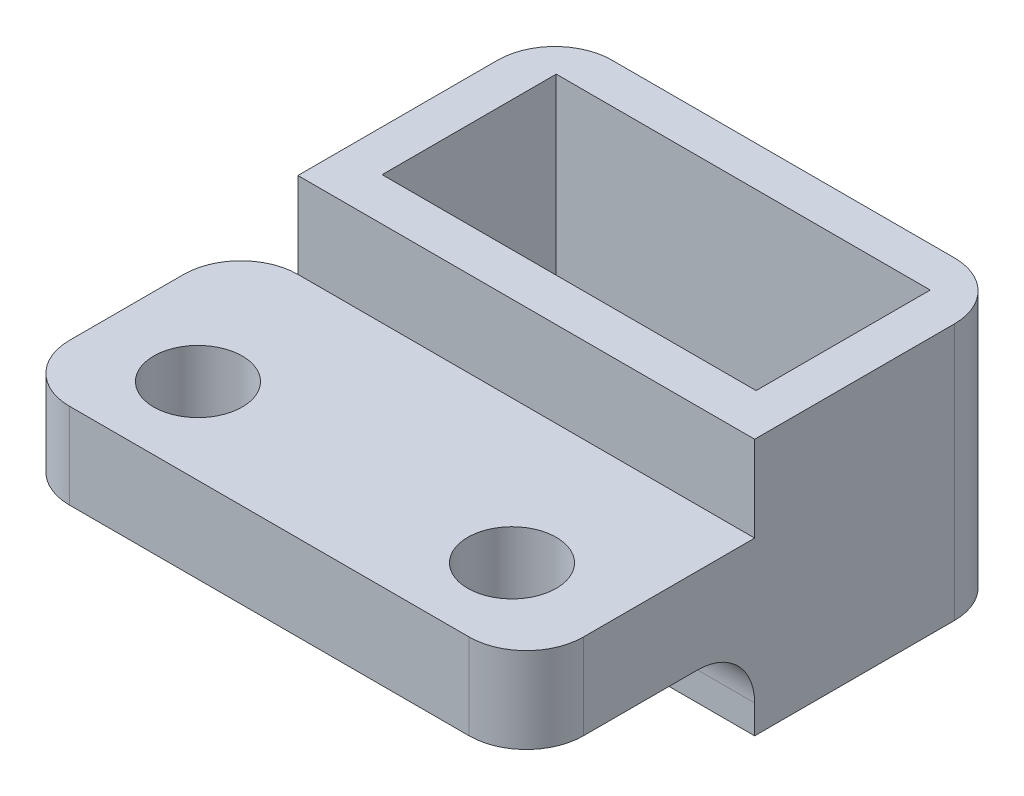
SolidWorks part; units mm, degrees
ref_plane "Alzado" through (0, 0, 0) normal (0, 0, 1) x (1, 0, 0)
ref_plane "Planta" through (0, 0, 0) normal (0, 1, 0) x (1, 0, 0)
ref_plane "Vista lateral" through (0, 0, 0) normal (1, 0, 0) x (0, 0, -1)
sketch "Croquis1" plane through (0, 0, 0) normal (0, 1, 0) x (1, 0, 0)
  line L0 (9, 18) -> (9, 0) construction
  line L1 (0, 0) -> (18, 0)
  line L2 (0, 0) -> (0, 18)
  line L3 (0, 18) -> (18, 18)
  line L4 (18, 0) -> (18, 18)
  circle A0 centre (3.5, 3) radius 1.55
  circle A1 centre (14.5, 3) radius 1.55
  dimension "D3" = 3.1
  dimension "D4" = 3
  dimension "D5" = 3.5
  dimension "D7" = 3
  dimension "D1" = 18
  dimension "D2" = 18
  dimension "D6" = 3.5
extrude "Saliente-Extruir1" add sketch "Croquis1" along normal blind 3
sketch "Croquis3" plane through (0, 3, 0) normal (0, 1, 0) x (1, 0, 0)
  line L0 (18, 0) -> (18, 18) construction
  line L1 (0, 18) -> (18, 18)
  line L2 (0, 18) -> (0, 8)
  line L3 (0, 8) -> (18, 8)
  line L4 (18, 18) -> (18, 8)
  dimension "D1" = 10
extrude "Saliente-Extruir3" add sketch "Croquis3" along normal blind 3
sketch "Croquis4" plane through (0, 0, 0) normal (0, -1, 0) x (1, 0, 0)
  line L1 (0, -18) -> (2, -18)
  line L2 (0, -18) -> (0, -8)
  line L3 (0, -8) -> (2, -8)
  line L4 (2, -18) -> (2, -8)
  dimension "D1" = 10
  dimension "D2" = 2
extrude "Cortar-Extruir1" cut sketch "Croquis4" against normal up to surface (6 mm away) up to face at (9, 6, -13)
sketch "Croquis7" plane through (0, 6, 0) normal (0, 1, 0) x (1, 0, 0)
  line L1 (3.45, 15.6) -> (16.55, 15.6)
  line L2 (3.45, 15.6) -> (3.45, 9.5)
  line L3 (3.45, 9.5) -> (16.55, 9.5)
  line L4 (16.55, 15.6) -> (16.55, 9.5)
  line L5 (2, 8) -> (18, 8) construction
  line L6 (2, 18) -> (2, 8) construction
  dimension "D1" = 6.1
  dimension "D2" = 13.1
  dimension "D3" = 1.5
  dimension "D4" = 1.45
extrude "Cortar-Extruir2" cut sketch "Croquis7" against normal up to surface (6 mm away) up to face at (6.6667, 0, -8.6667)
sketch "Croquis9" plane through (0, 0, 0) normal (0, -1, 0) x (1, 0, 0)
  line L0 (16.55, -15.6) -> (3.45, -15.6) construction
  line L1 (18, -18) -> (2, -18)
  line L2 (18, -18) -> (18, -8)
  line L3 (18, -8) -> (2, -8)
  line L4 (2, -18) -> (2, -8)
  line L5 (3.45, -15.6) -> (3.45, -9.5) construction
  line L6 (3.45, -9.5) -> (16.55, -9.5) construction
  line L7 (16.55, -9.5) -> (16.55, -15.6) construction
  line L8 (3.45, -9.5) -> (16.55, -9.5)
  line L9 (3.45, -15.6) -> (3.45, -9.5)
  line L10 (16.55, -15.6) -> (3.45, -15.6)
  line L11 (16.55, -9.5) -> (16.55, -15.6)
extrude "Saliente-Extruir4" add sketch "Croquis9" along normal blind 3
sketch "Croquis10" plane through (0, -3, 0) normal (0, -1, 0) x (1, 0, 0)
  line L0 (16.55, -15.6) -> (16.55, -9.5) construction
  line L1 (16.55, -9.5) -> (3.45, -9.5) construction
  line L2 (3.45, -9.5) -> (3.45, -15.6) construction
  line L3 (3.45, -15.6) -> (16.55, -15.6) construction
  line L4 (16.55, -15.6) -> (16.55, -9.5)
  line L5 (16.55, -9.5) -> (3.45, -9.5)
  line L6 (3.45, -9.5) -> (3.45, -15.6)
  line L7 (3.45, -15.6) -> (16.55, -15.6)
  line L8 (15.8, -14.85) -> (15.8, -10.25)
  line L9 (15.8, -10.25) -> (4.2, -10.25)
  line L10 (4.2, -10.25) -> (4.2, -14.85)
  line L11 (4.2, -14.85) -> (15.8, -14.85)
  dimension "D1" = 0.75
extrude "Saliente-Extruir6" add sketch "Croquis10" against normal blind 2.5
sketch "Croquis11" plane through (0, 6, 0) normal (0, 1, 0) x (1, 0, 0)
  line L0 (18, 8) -> (18, 18) construction
  line L1 (2, 18) -> (18, 18)
  line L2 (2, 18) -> (2, 17)
  line L3 (2, 17) -> (18, 17)
  line L4 (18, 18) -> (18, 17)
  dimension "D1" = 1
extrude "Cortar-Extruir4" cut sketch "Croquis11" against normal up to surface (9 mm away) up to face at (10, -3, -13)
fillet "Redondeo1" radius 2 6 edges at (18, 1.5, -17) (2, 1.5, -17) (0, 1.5, -8) (10, 0, -8) (18, 1.5, 0) (0, 1.5, 0)
